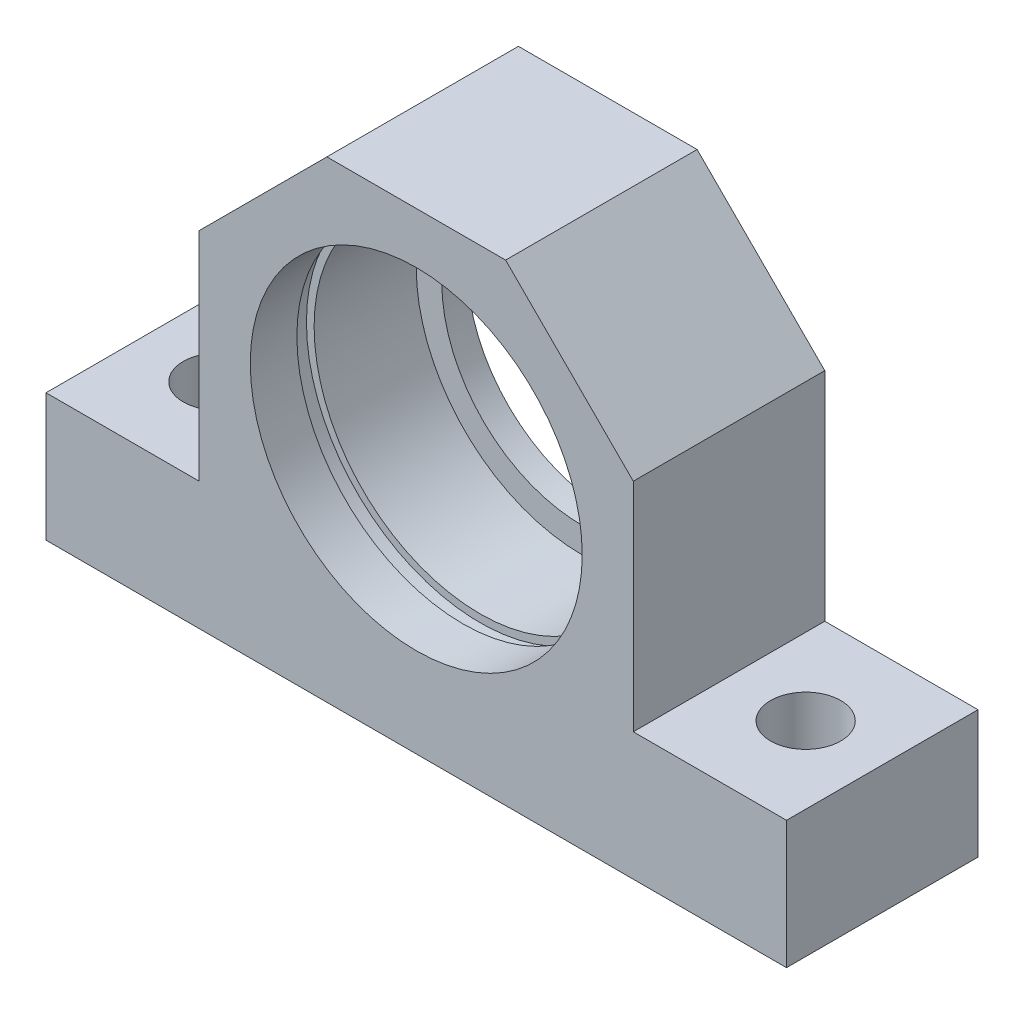
SolidWorks part; units mm, degrees
ref_plane "Front Plane" through (0, 0, 0) normal (0, 0, 1) x (1, 0, 0)
ref_plane "Top Plane" through (0, 0, 0) normal (0, 1, 0) x (1, 0, 0)
ref_plane "Right Plane" through (0, 0, 0) normal (1, 0, 0) x (0, 0, -1)
sketch "Sketch1" plane through (0, 0, 0) normal (0, 0, 1) x (1, 0, 0)
  line L0 (-17, 37) -> (17, 37)
  line L1 (17, 37) -> (17, 10)
  line L2 (17, 10) -> (29, 10)
  line L3 (29, 10) -> (29, 0)
  line L4 (29, 0) -> (-29, 0)
  line L5 (-29, 0) -> (-29, 10)
  line L6 (-29, 10) -> (-17, 10)
  line L7 (-17, 10) -> (-17, 37)
  line L8 (0, 37) -> (0, 0) construction
  point P12 (0, 20)
  dimension "L" = 58
  dimension "S" = 10
  dimension "L2" = 34
  dimension "H_s" = 20
  dimension "H" = 37
  dimension "MSM_6" = 17
extrude "Boss-Extrude1" add sketch "Sketch1" against normal blind 15
sketch "Sketch2" plane through (0, 0, 0) normal (1, 0, 0) x (0, 0, -1)
  line L0 (15, 20) -> (0, 20) construction
  line L1 (3.65, 33) -> (3.65, 33.6)
  line L2 (13, 33) -> (5, 33)
  line L3 (13, 33) -> (13, 31)
  line L4 (13, 31) -> (15, 31)
  line L5 (3.65, 33.6) -> (5, 33.6)
  line L6 (5, 33.6) -> (5, 33)
  line L7 (0, 33) -> (0, 20)
  line L8 (0, 20) -> (15, 20)
  line L9 (15, 20) -> (15, 31)
  line L11 (0, 10) -> (0, 37) construction
  line L12 (3.65, 33) -> (0, 33)
  line L13 (0, 10) -> (0, 37) construction
  line L14 (15, 10) -> (15, 37) construction
  dimension "D" = 26
  dimension "DH_s" = 22
  dimension "B" = 8
  dimension "H_s" = 20
  dimension "L1_s" = 2
  dimension "MSM_2" = 1.35
  dimension "MSM_1" = 27.2
revolve "Cut-Revolve1" cut sketch "Sketch2" angle 360 about L0
hole_wizard "Diameter Hole1" positions "Sketch4" profile "Sketch3" hole size "Ø5.5" standard "JIS" end condition through all
sketch "Sketch4" plane through (0, 10, 0) normal (0, 1, 0) x (1, 0, 0)
  line L10 (0, 0) -> (0, 15) construction
  line L11 (17, 15) -> (-17, 15) construction
  line L12 (-29, 7.5) -> (29, 7.5) construction
  line L13 (-29, 15) -> (-29, 0) construction
  line L14 (29, 15) -> (29, 0) construction
  point P0 (-23, 7.5)
  point P6 (23, 7.5)
  dimension "L1" = 46
  dimension "T/2" = 7.5
sketch "Sketch3" plane through (-23, 10, -7.5) normal (1, 0, 0) x (0, 0, 1)
  line L0 (0, 0) -> (0, 10)
  line L1 (0, 10) -> (2.75, 10)
  line L2 (2.75, 10) -> (2.75, 0)
  line L5 (2.75, 0) -> (0, 0)
  line L11 (0, 0) -> (0, 10) construction
  dimension "D1_s" = 5.5
  dimension "Thru Hole Depth" = 10
chamfer "Chamfer1" distance 10 angle 45 2 edges at (-17, 37, -7.5) (17, 37, -7.5)
chamfer "Chamfer2" [suppressed] distance 2 angle 45
